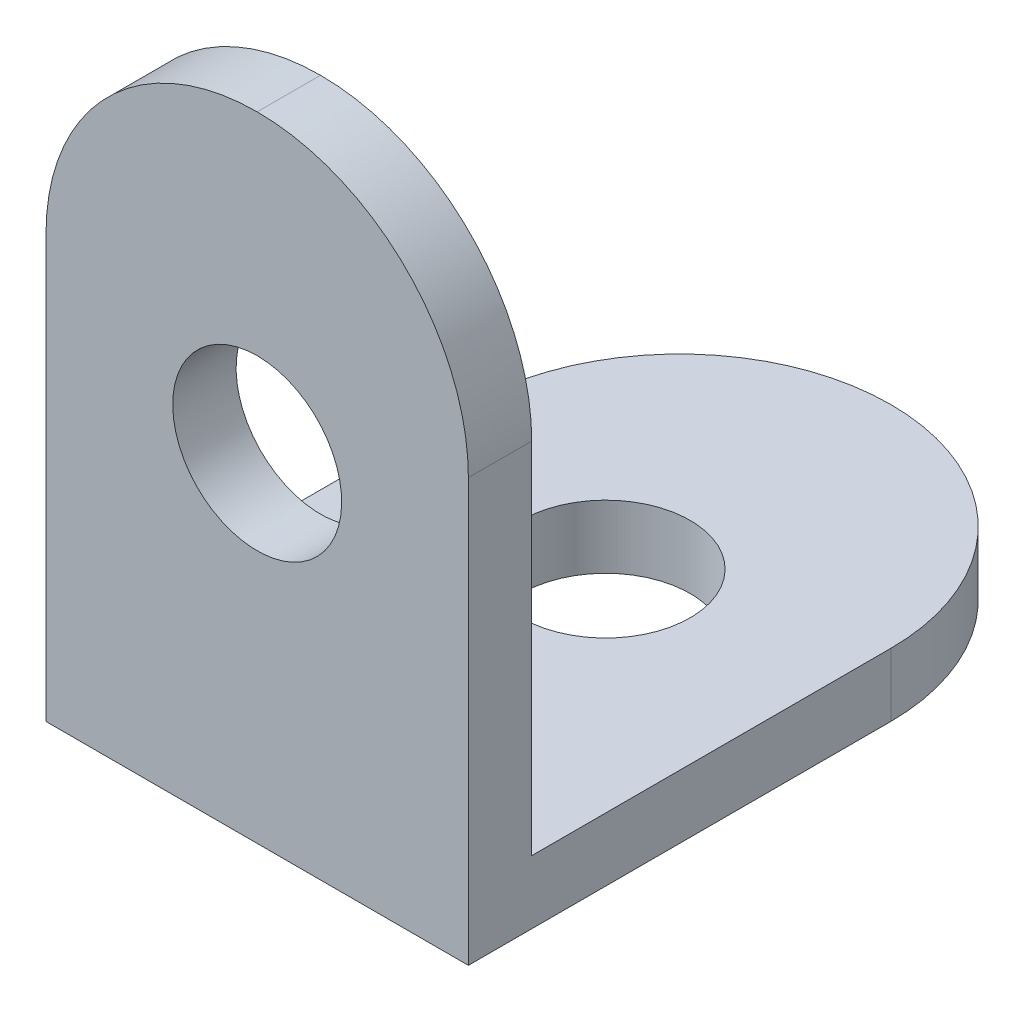
SolidWorks part; units mm, degrees
ref_plane "Plan de face" through (0, 0, 0) normal (0, 0, 1) x (1, 0, 0)
ref_plane "Plan de dessus" through (0, 0, 0) normal (0, 1, 0) x (1, 0, 0)
ref_plane "Plan de droite" through (0, 0, 0) normal (1, 0, 0) x (0, 0, -1)
sketch "Esquisse1" plane through (0, 0, 0) normal (1, 0, 0) x (0, 0, -1)
  line L0 (6.75, 0) -> (-6.75, 0)
  line L1 (-6.75, 0) -> (-6.75, 13.5)
  line L2 (-6.75, 13.5) -> (-8.25, 13.5)
  line L3 (-8.25, 13.5) -> (-8.25, -1.5)
  line L4 (-8.25, -1.5) -> (6.75, -1.5)
  line L5 (6.75, -1.5) -> (6.75, 0)
  dimension "D1" = 15
  dimension "D2" = 15
  dimension "D3" = 1.5
  dimension "D4" = 1.5
extrude "Boss.-Extru.1" add sketch "Esquisse1" along normal blind 10
sketch "Esquisse2" plane through (0, 0, 6.75) normal (0, 0, -1) x (-1, 0, 0)
  line L0 (-10, 13.5) -> (0, 13.5) construction
  circle A0 centre (-5, 6.5) radius 2
  point P4 (-5, 13.5)
  dimension "D1" = 4
  dimension "D2" = 7
extrude "Enlèv. mat.-Extru.1" cut sketch "Esquisse2" against normal through all
fillet "Congé1" radius 5 2 edges at (0, 13.5, 7.5) (10, 13.5, 7.5)
sketch "Esquisse3" plane through (0, 0, 0) normal (0, 1, 0) x (1, 0, 0)
  line L0 (10, 6.75) -> (0, 6.75) construction
  circle A0 centre (5, 0) radius 2
  point P4 (5, 6.75)
  point P5 (0, 0)
  point P8 (0, 0)
  dimension "D1" = 4
extrude "Enlèv. mat.-Extru.2" cut sketch "Esquisse3" against normal through all
fillet "Congé2" radius 5 2 edges at (10, -0.75, -6.75) (0, -0.75, -6.75)
